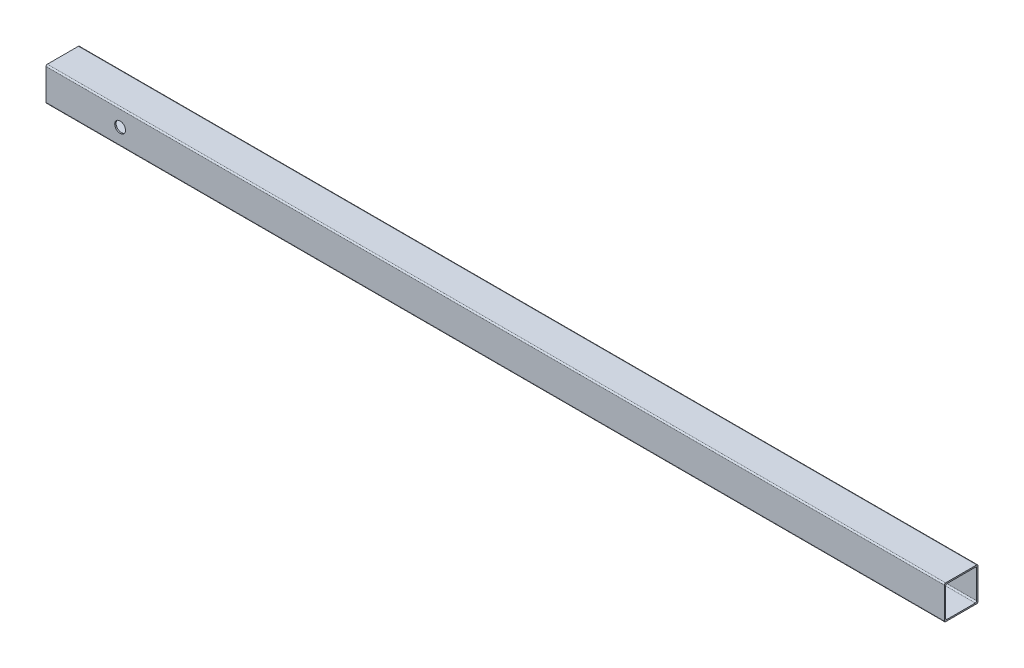
SolidWorks part; units mm, degrees
material "Thornel Mat VMA"
ref_plane "Front Plane" through (0, 0, 0) normal (0, 0, 1) x (1, 0, 0)
ref_plane "Top Plane" through (0, 0, 0) normal (0, 1, 0) x (1, 0, 0)
ref_plane "Right Plane" through (0, 0, 0) normal (1, 0, 0) x (0, 0, -1)
sketch "Sketch2" plane through (0, 0, 0) normal (1, 0, 0) x (0, 0, -1)
  line L1 (0.762, 0) -> (18.288, 0)
  line L2 (0, 0.762) -> (0, 18.288)
  line L3 (0.762, 19.05) -> (18.288, 19.05)
  line L4 (19.05, 0.762) -> (19.05, 18.288)
  line L5 (1.524, 0.762) -> (17.526, 0.762)
  line L6 (0.762, 1.524) -> (0.762, 17.526)
  line L7 (1.524, 18.288) -> (17.526, 18.288)
  line L8 (18.288, 1.524) -> (18.288, 17.526)
  arc A0 (17.526, 18.288) -> (18.288, 17.526) centre (17.526, 17.526) cw
  arc A1 (17.526, 0.762) -> (18.288, 1.524) centre (17.526, 1.524) ccw
  arc A2 (1.524, 0.762) -> (0.762, 1.524) centre (1.524, 1.524) cw
  arc A3 (0.762, 17.526) -> (1.524, 18.288) centre (1.524, 17.526) cw
  arc A4 (18.288, 19.05) -> (19.05, 18.288) centre (18.288, 18.288) cw
  arc A5 (18.288, 0) -> (19.05, 0.762) centre (18.288, 0.762) ccw
  arc A6 (0.762, 0) -> (0, 0.762) centre (0.762, 0.762) cw
  arc A7 (0, 18.288) -> (0.762, 19.05) centre (0.762, 18.288) cw
  point P11 (18.288, 18.288)
  point P14 (18.288, 0.762)
  point P19 (0.762, 18.288)
  point P22 (19.05, 19.05)
  point P25 (19.05, 0)
  point P28 (0, 0)
  point P31 (0, 19.05)
  dimension "D7" = 0.762
  dimension "D1" = 19.05
  dimension "D2" = 19.05
  dimension "D5" = 0.762
  dimension "D6" = 0.762
  dimension "D3" = 0.762
  dimension "D4" = 0.762
extrude "Boss-Extrude1" add sketch "Sketch2" along normal blind 50.8
sketch "Sketch3" plane through (0, 0, 0) normal (0, 0, 1) x (1, 0, 0)
  line L0 (0, 18.288) -> (0, 0.762) construction
  line L1 (50.8, 19.05) -> (0, 19.05) construction
  circle A0 centre (41.91, 9.525) radius 3.048
  dimension "D1" = 6.096
  dimension "D2" = 41.91
  dimension "D3" = 9.525
extrude "Cut-Extrude1" cut sketch "Sketch3" against normal up to surface (19.05 mm away) up to face at (25.4, 9.525, -19.05)
sketch "Sketch4" plane through (50.8, 0, 0) normal (1, 0, 0) x (0, 0, -1)
  line L1 (0, 12.573) -> (0, 6.477)
  line L2 (0, 12.573) -> (0, 6.477)
  line L6 (19.05, 0.762) -> (19.05, 18.288)
  line L7 (0.762, 0) -> (18.288, 0)
  line L8 (0, 18.288) -> (0, 0.762)
  line L9 (18.288, 19.05) -> (0.762, 19.05)
  line L10 (19.05, 0.762) -> (19.05, 18.288)
  line L11 (0.762, 0) -> (18.288, 0)
  line L12 (0, 18.288) -> (0, 0.762)
  line L13 (18.288, 19.05) -> (0.762, 19.05)
  arc A4 (19.05, 18.288) -> (18.288, 19.05) centre (18.288, 18.288) ccw
  arc A5 (18.288, 0) -> (19.05, 0.762) centre (18.288, 0.762) ccw
  arc A6 (0, 0.762) -> (0.762, 0) centre (0.762, 0.762) ccw
  arc A7 (0.762, 19.05) -> (0, 18.288) centre (0.762, 18.288) ccw
  arc A8 (19.05, 18.288) -> (18.288, 19.05) centre (18.288, 18.288) ccw
  arc A9 (18.288, 0) -> (19.05, 0.762) centre (18.288, 0.762) ccw
  arc A10 (0, 0.762) -> (0.762, 0) centre (0.762, 0.762) ccw
  arc A11 (0.762, 19.05) -> (0, 18.288) centre (0.762, 18.288) ccw
  arc M10 (19.05, 18.288) -> (18.288, 19.05) centre (18.288, 18.288) ccw
  line M11 (18.288, 19.05) -> (0.762, 19.05)
  arc M12 (0.762, 19.05) -> (0, 18.288) centre (0.762, 18.288) ccw
  line M13 (0, 18.288) -> (0, 0.762)
  arc M14 (0, 0.762) -> (0.762, 0) centre (0.762, 0.762) ccw
  line M15 (0.762, 0) -> (18.288, 0)
  arc M16 (18.288, 0) -> (19.05, 0.762) centre (18.288, 0.762) ccw
  line M17 (19.05, 0.762) -> (19.05, 18.288)
  arc M18 (17.526, 18.288) -> (18.288, 17.526) centre (17.526, 17.526) cw
  line M19 (18.288, 17.526) -> (18.288, 1.524)
  arc M20 (18.288, 1.524) -> (17.526, 0.762) centre (17.526, 1.524) cw
  line M21 (17.526, 0.762) -> (1.524, 0.762)
  arc M22 (1.524, 0.762) -> (0.762, 1.524) centre (1.524, 1.524) cw
  line M23 (0.762, 1.524) -> (0.762, 17.526)
  arc M24 (0.762, 17.526) -> (1.524, 18.288) centre (1.524, 17.526) cw
  line M25 (1.524, 18.288) -> (17.526, 18.288)
  dimension "D1" = 0
  dimension "D2" = 0
extrude "Boss-Extrude2" add sketch "Sketch4" along normal blind 457.2 contours M17 M10 M11 M12 M13 M14 M15 M16 M25 M18 M19 M20 M21 M22 M23 M24 region at (50.8, 15.4305, -0.2694)
equation "\"shaft\"=0.75"
equation "\"D1@Sketch2\"=\"shaft\""
equation "\"D2@Sketch2\"=\"shaft\""
equation "\"IDshaft\"=0.4375"
equation "\"D3@Sketch3\"=\"shaft\"/2"
